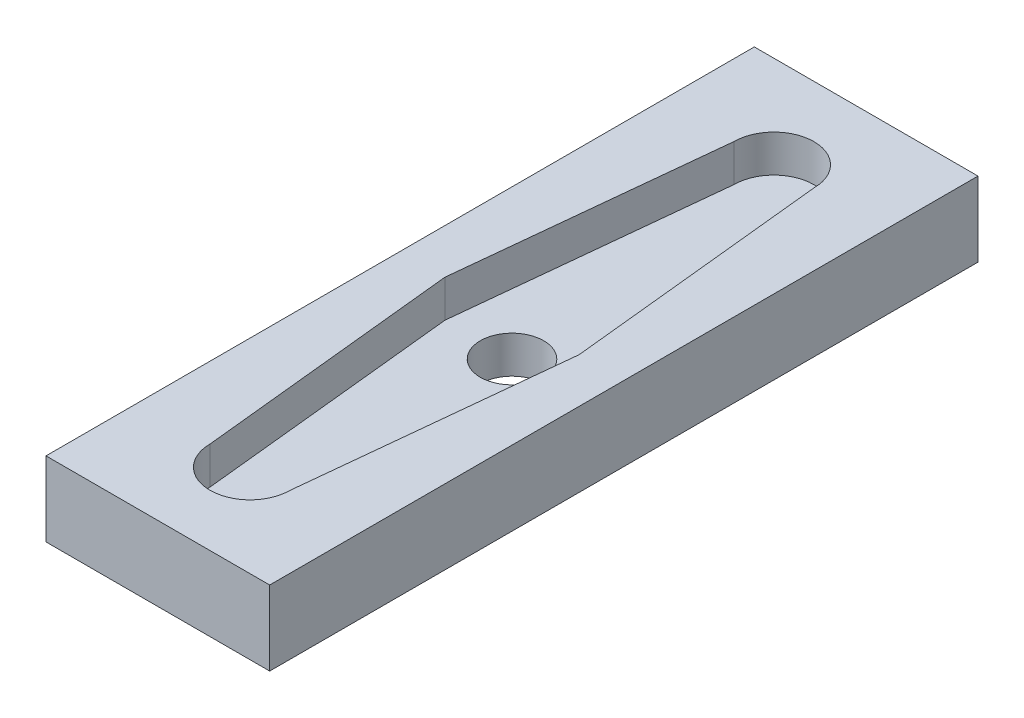
SolidWorks part; units mm, degrees
ref_plane "Front Plane" through (0, 0, 0) normal (0, 0, 1) x (1, 0, 0)
ref_plane "Top Plane" through (0, 0, 0) normal (0, 1, 0) x (1, 0, 0)
ref_plane "Right Plane" through (0, 0, 0) normal (1, 0, 0) x (0, 0, -1)
sketch "Sketch1" plane through (0, 0, 0) normal (0, 1, 0) x (1, 0, 0)
  line L1 (0, 0) -> (20, 0)
  line L2 (0, 0) -> (0, 50)
  line L3 (0, 50) -> (20, 50)
  line L4 (20, 0) -> (20, 50)
  dimension "D1" = 50
  dimension "D2" = 20
extrude "Boss-Extrude2" add sketch "Sketch1" along normal blind 4
sketch "Sketch3" plane through (0, 4, 0) normal (0, 1, 0) x (1, 0, 0)
  line L0 (7.85, 10.95) -> (6.4, 25)
  line L1 (6.4, 25) -> (7.85, 39.05)
  line L2 (12.15, 39.05) -> (13.6, 25)
  line L3 (13.6, 25) -> (12.15, 10.95)
  line L4 (6.4, 25) -> (13.6, 25) construction
  line L5 (20, 50) -> (0, 50) construction
  line L6 (0, 50) -> (0, 0) construction
  arc A0 (12.15, 39.05) -> (7.85, 39.05) centre (10, 39.05) ccw
  arc A1 (7.85, 10.95) -> (12.15, 10.95) centre (10, 10.95) ccw
  point P12 (10, 50)
  point P15 (0, 25)
  dimension "D1" = 4.3
  dimension "D2" = 4.3
  dimension "D3" = 28.1
  dimension "D4" = 14.05
  dimension "D5" = 7.2
  dimension "D6" = 3.6
  dimension "D7" = 3.6
extrude "Cut-Extrude1" cut sketch "Sketch3" against normal blind 2
sketch "Sketch4" plane through (0, 4, 0) normal (0, 1, 0) x (1, 0, 0)
  line L1 (0, 50) -> (20, 50)
  line L2 (0, 50) -> (0, 0)
  line L3 (0, 0) -> (20, 0)
  line L4 (20, 50) -> (20, 0)
  line L5 (4, 44) -> (16, 44)
  line L6 (4, 44) -> (4, 6)
  line L7 (4, 6) -> (16, 6)
  line L8 (16, 44) -> (16, 6)
  dimension "D1" = 4
  dimension "D2" = 4
  dimension "D3" = 6
  dimension "D4" = 6
extrude "Cut-Extrude2" cut sketch "Sketch4" against normal through all
sketch "Sketch5" plane through (0, 2, 0) normal (0, 1, 0) x (1, 0, 0)
  line L0 (6.4, 25) -> (13.6, 25) construction
  circle A0 centre (10, 25) radius 1.7
  dimension "D1" = 3.4
extrude "Cut-Extrude3" cut sketch "Sketch5" against normal blind 2
